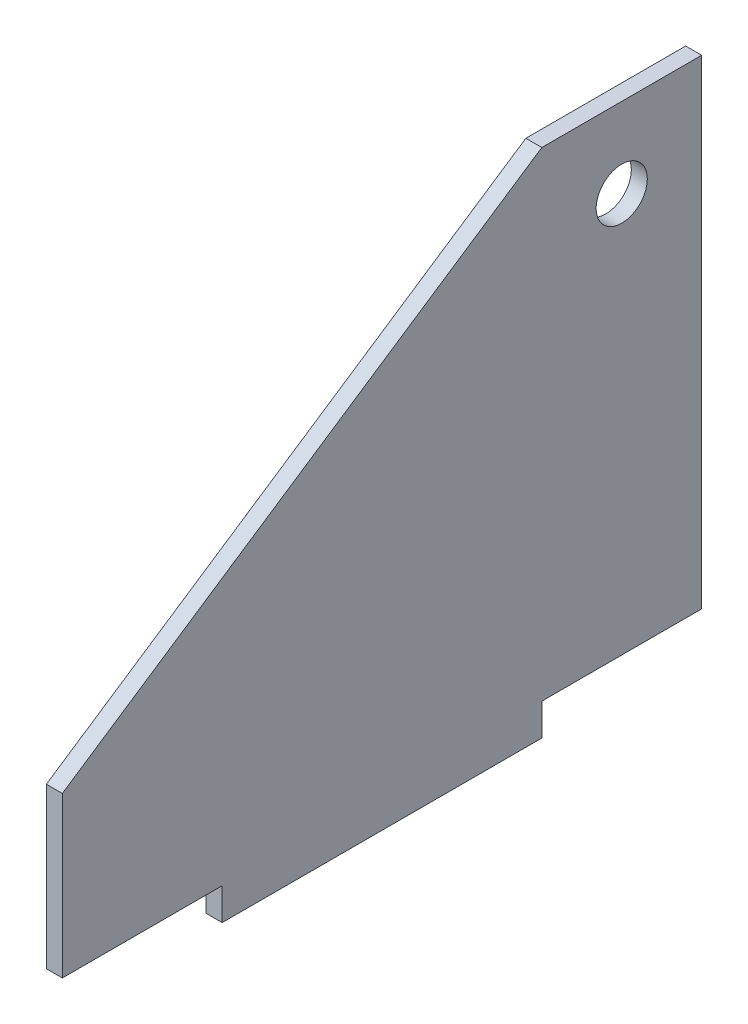
SolidWorks part; units mm, degrees
ref_plane "Alzado" through (0, 0, 0) normal (0, 0, 1) x (1, 0, 0)
ref_plane "Planta" through (0, 0, 0) normal (0, 1, 0) x (1, 0, 0)
ref_plane "Vista lateral" through (0, 0, 0) normal (1, 0, 0) x (0, 0, -1)
sketch "Croquis1" plane through (0, 0, 0) normal (1, 0, 0) x (0, 0, -1)
  line L0 (50, 75) -> (-100, -25)
  line L1 (-100, -75) -> (-50, -75)
  line L2 (-100, -75) -> (-100, -25)
  line L3 (50, 75) -> (100, 75)
  line L4 (100, -75) -> (100, 75)
  line L5 (100, 0) -> (-62.5, 0) construction
  line L6 (75, 75) -> (75, -75) construction
  line L7 (0, 41.6667) -> (0, -85) construction
  line L9 (-50, -75) -> (-50, -85)
  line L10 (-50, -85) -> (50, -85)
  line L11 (50, -75) -> (50, -85)
  line L14 (50, -75) -> (100, -75)
  circle A0 centre (75, 50) radius 8
  point P0 (0, 0)
  point P13 (0, -75)
  dimension "D6" = 16
  dimension "D1" = 150
  dimension "D2" = 200
  dimension "D3" = 50
  dimension "D4" = 50
  dimension "D5" = 50
  dimension "D7" = 100
  dimension "D8" = 50
  dimension "D9" = 10
extrude "Saliente-Extruir1" add sketch "Croquis1" along normal blind 5
